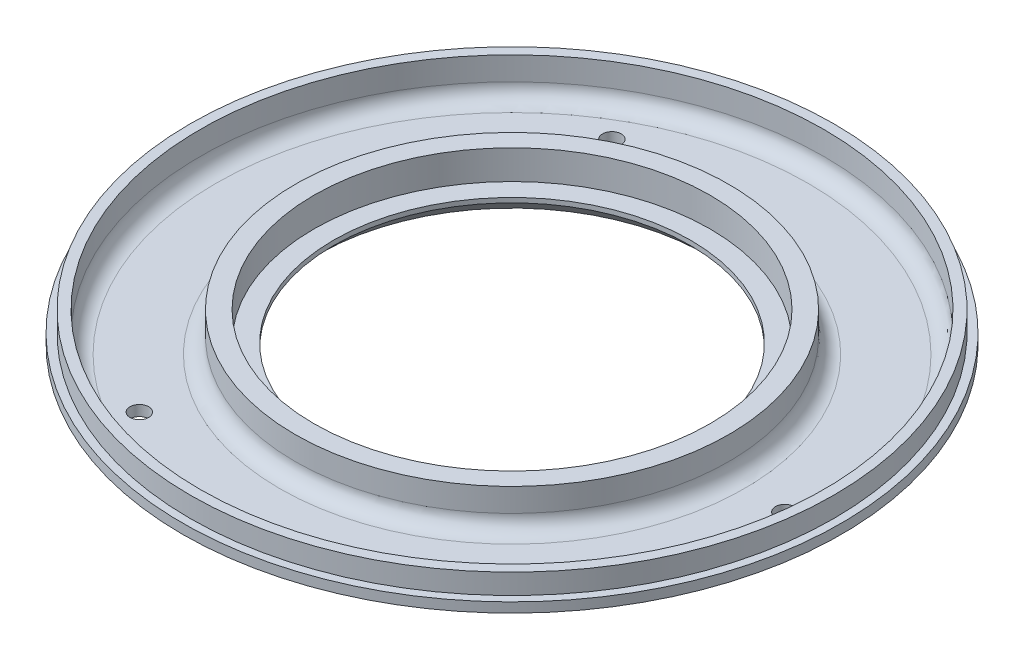
SolidWorks part; units mm, degrees
material "6061-T6 (SS)"
ref_plane "Front Plane" through (0, 0, 0) normal (0, 0, 1) x (1, 0, 0)
ref_plane "Top Plane" through (0, 0, 0) normal (0, 1, 0) x (1, 0, 0)
ref_plane "Right Plane" through (0, 0, 0) normal (1, 0, 0) x (0, 0, -1)
sketch "Sketch2" plane through (0, 0, 0) normal (1, 0, 0) x (0, 0, -1)
  line L0 (-45.8, 0) -> (-82.55, 0)
  line L1 (-82.55, 0) -> (-82.55, 12.7)
  line L2 (-82.55, 12.7) -> (-50.8, 12.7)
  line L3 (-45.8, 0) -> (-45.8, 5.2)
  line L4 (-45.8, 5.2) -> (-50.8, 5.2)
  line L5 (-50.8, 5.2) -> (-50.8, 12.7)
  line L6 (-80.2166, 12.7) -> (-80.2166, 0) construction
  dimension "D1" = 82.55
  dimension "D2" = 12.7
  dimension "D3" = 50.8
  dimension "D4" = 5
  dimension "D5" = 7.5
ref_axis "Axis1" through (0, -0.9004, 0) along (0, 1, 0)
revolve "Revolve1" add sketch "Sketch2" angle 360 about axis through (0, -0.9004, 0) along (0, 1, 0)
hole_wizard "#90 (0.0087) Diameter Hole1" positions "Sketch6" profile "Sketch7" hole size "#90" standard "ANSI Inch" end condition through all
sketch "Sketch6" plane through (0, 12.7, 0) normal (0, 1, 0) x (1, 0, 0)
  line L0 (0, 0) -> (-69.8201, 120.932) construction
  line L2 (0, 0) -> (0, 109.0908) construction
  point P0 (-35, 60.6218)
  dimension "D1" = 30
  dimension "D2" = 70
sketch "Sketch7" plane through (-35, 12.7, -60.6218) normal (1, 0, 0) x (0, 0, 1)
  line L0 (0, 0) -> (0, 12.7)
  line L1 (0, 12.7) -> (0.1105, 12.7)
  line L2 (0.1105, 12.7) -> (0.1105, 0)
  line L5 (0.1105, 0) -> (0, 0)
  line L11 (0, -6.35) -> (0, 107.95) construction
  dimension "Thru Hole Dia." = 0.221
  dimension "Thru Hole Depth" = 12.7
pattern_circular "CirPattern3" count 3 over 360 about axis through (0, -0.9004, 0) along (0, 1, 0) of "#90 (0.0087) Diameter Hole1"
sketch "Sketch8" plane through (0, 12.7, 0) normal (0, 1, 0) x (1, 0, 0)
  circle A0 centre (0, 0) radius 55.626
  circle A1 centre (0, 0) radius 80.01
  circle A2 centre (0, 0) radius 82.55 construction
  dimension "D1" = 26.924
  dimension "D2" = 2.54
extrude "Cut-Extrude1" cut sketch "Sketch8" against normal blind 10
fillet "Fillet5" radius 4 2 edges at (0, 2.7, 55.626) (0, 2.7, 80.01)
chamfer "Chamfer1" distance 4 angle 45 1 edges at (0, 0, -45.8)
sketch "Sketch10" plane through (0, 0, 0) normal (0, -1, 0) x (1, 0, 0)
  circle A0 centre (0, 0) radius 82.55
  circle A1 centre (0, 0) radius 84.55
  circle A2 centre (0, 0) radius 82.55 construction
  dimension "D1" = 2
extrude "Boss-Extrude1" add sketch "Sketch10" against normal blind 7.5
chamfer "Chamfer3" distance 5 angle 60 1 edges at (0, 0, -84.55) first distance on face at (0, 7.5, -84.55)
fillet "Fillet4" radius 5 1 edges at (0, 0, 75.8897)
hole_wizard "#12 (0.189) Diameter Hole1" positions "Sketch13" profile "Sketch14" hole size "#12" standard "ANSI Inch" end condition through all
sketch "Sketch13" plane through (0, 0, 0) normal (0, -1, 0) x (-1, 0, 0)
  point P4 (35, 60.6218)
sketch "Sketch14" plane through (-35, 0, -60.6218) normal (1, 0, 0) x (0, 0, -1)
  line L0 (0, 0) -> (0, 12.7)
  line L1 (0, 12.7) -> (2.4003, 12.7)
  line L2 (2.4003, 12.7) -> (2.4003, 0)
  line L5 (2.4003, 0) -> (0, 0)
  line L11 (0, -6.35) -> (0, 107.95) construction
  dimension "Thru Hole Dia." = 4.8006
  dimension "Thru Hole Depth" = 12.7
pattern_circular "CirPattern5" count 3 over 360 about axis through (0, -0.9004, 0) along (0, 1, 0) of "#12 (0.189) Diameter Hole1"
equation "\"TubeDiameter\" = 6.500in"
